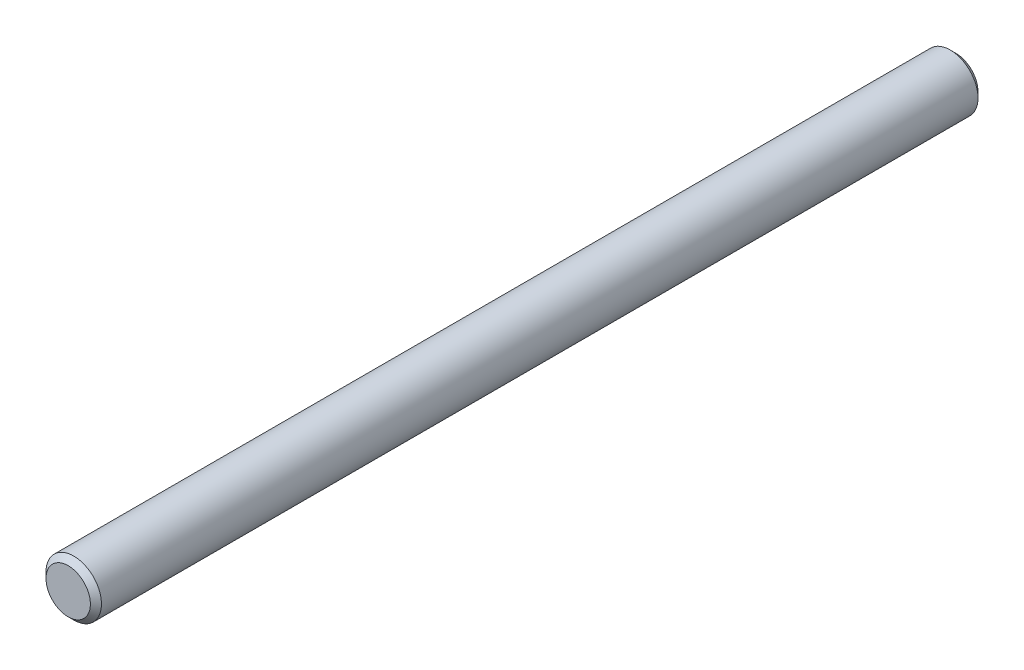
SolidWorks part; units mm, degrees
ref_plane "Front" through (0, 0, 0) normal (0, 0, 1) x (1, 0, 0)
ref_plane "Top" through (0, 0, 0) normal (0, 1, 0) x (1, 0, 0)
ref_plane "Right" through (0, 0, 0) normal (1, 0, 0) x (0, 0, -1)
sketch "Sketch1" plane through (0, 0, 0) normal (0, 0, 1) x (1, 0, 0)
  circle A0 centre (0, 0) radius 9.525
  dimension "dia" = 19.05
extrude "Extrude1" add sketch "Sketch1" along normal mid plane 304.8
sketch "Sketch2" plane through (0, 0, 0) normal (1, 0, 0) x (0, 0, -1)
  line L0 (152.4, 9.525) -> (149.86, 9.525) construction
  line L1 (152.4, 9.525) -> (-152.4, 9.525) construction
  line L2 (149.86, 9.525) -> (118.9037, 9.525) construction
  line L3 (118.9037, 9.525) -> (111.76, 9.525) construction
  line L4 (111.76, 9.525) -> (109.22, 9.525) construction
  line L5 (109.22, 9.525) -> (107.7011, 9.525) construction
  line L7 (101.3511, 9.525) -> (96.4159, 9.525) construction
  line L8 (96.4159, 9.525) -> (86.4006, 9.525) construction
  line L10 (-152.4, -9.525) -> (152.4, -9.525) construction
  line L11 (-152.4, 9.525) -> (-149.86, 9.525) construction
  line L12 (-149.86, 9.525) -> (-149.86, -9.525) construction
  line L13 (107.7011, 9.525) -> (101.3511, 9.525) construction
  line L14 (101.3511, 9.525) -> (101.3511, -9.525) construction
  line L15 (111.76, 9.525) -> (111.76, -9.525) construction
  line L16 (86.4006, 9.525) -> (81.4654, 9.525) construction
  line L17 (81.4654, 9.525) -> (71.4578, 9.525) construction
  line L18 (71.4578, 9.525) -> (66.5226, 9.525) construction
  line L19 (66.5226, 9.525) -> (56.515, 9.525) construction
  line L20 (86.4006, 9.525) -> (86.4006, -9.525) construction
  line L21 (71.4578, 9.525) -> (71.4578, -9.525) construction
  line L22 (56.515, 9.525) -> (56.515, -9.525) construction
  line L23 (56.515, 9.525) -> (51.5874, 9.525) construction
  line L24 (51.5874, 9.525) -> (41.5798, 9.525) construction
  line L25 (41.5798, 9.525) -> (41.5798, -9.525) construction
  line L26 (41.5798, 9.525) -> (36.6522, 9.525) construction
  line L27 (36.6522, 9.525) -> (26.6446, 9.525) construction
  line L28 (26.6446, 9.525) -> (21.717, 9.525) construction
  line L29 (21.717, 9.525) -> (11.7094, 9.525) construction
  line L30 (26.6446, 9.525) -> (26.6446, -9.525) construction
  line L31 (11.7094, 9.525) -> (11.7094, -9.525) construction
  line L32 (11.7094, 9.525) -> (6.7742, 9.525) construction
  line L33 (6.7742, 9.525) -> (0.4242, 9.525) construction
  line L34 (0.4242, 9.525) -> (-1.0947, 9.525) construction
  line L35 (-1.0947, 9.525) -> (-3.6347, 9.525) construction
  line L36 (-3.6347, 9.525) -> (-3.6347, -9.525) construction
  line L37 (-3.6347, 9.525) -> (-54.4347, 9.525) construction
  line L38 (-54.4347, 9.525) -> (-54.4347, -9.525) construction
  point P0 (-152.4, 9.525)
  point P1 (152.4, 9.525)
  dimension "D1" = 2.54
  dimension "D2" = 30.9562
  dimension "D3" = 7.1437
  dimension "D4" = 2.54
  dimension "D5" = 1.5189
  dimension "D6" = 6.35
  dimension "D7" = 10.0152
  dimension "D8" = 2.54
  dimension "D9" = 4.9352
  dimension "D10" = 4.9352
  dimension "D11" = 10.0076
  dimension "D12" = 4.9352
  dimension "D13" = 10.0076
  dimension "D14" = 4.9276
  dimension "D15" = 10.0076
  dimension "D16" = 4.9276
  dimension "D17" = 10.0076
  dimension "D18" = 4.9276
  dimension "D19" = 10.0076
  dimension "D20" = 4.9352
  dimension "D21" = 6.35
  dimension "D22" = 1.5189
  dimension "D23" = 2.54
  dimension "D24" = 50.8
chamfer "Chamfer1" distance 1.905 angle 45 2 edges at (9.525, 0, -152.4) (9.525, 0, 152.4)
equation "\"D1@Chamfer1\" = \"dia@Sketch1\" * .1"
